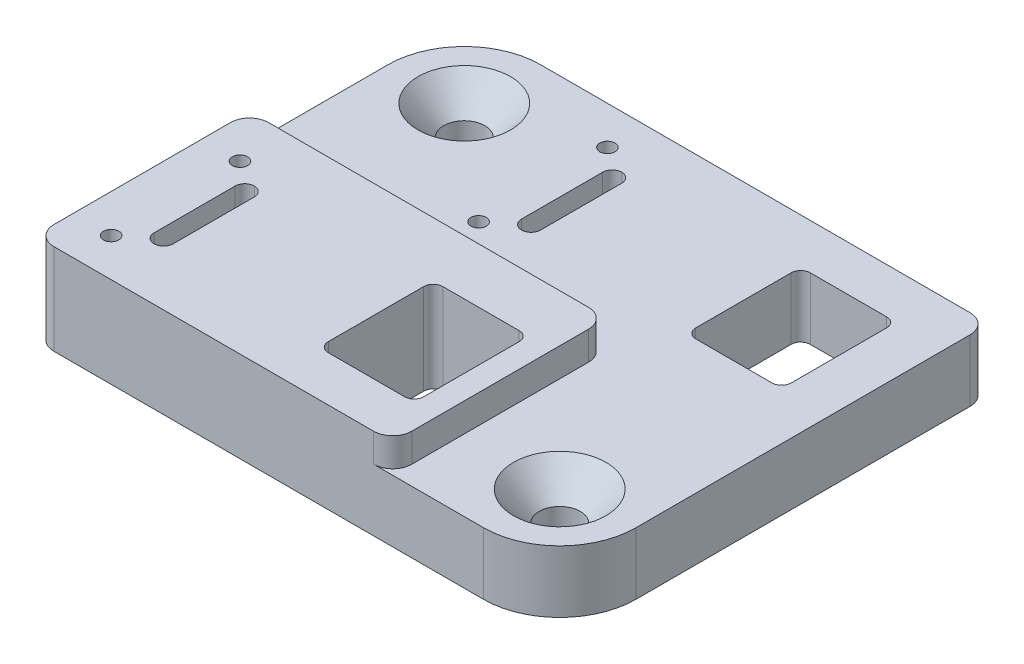
SolidWorks part; units mm, degrees
ref_plane "Top" through (0, 0, 0) normal (0, 0, 1) x (1, 0, 0)
ref_plane "Front" through (0, 0, 0) normal (0, 1, 0) x (1, 0, 0)
ref_plane "Right" through (0, 0, 0) normal (1, 0, 0) x (0, 0, -1)
sketch "Base Sketch" plane through (0, 0, 0) normal (0, 1, 0) x (1, 0, 0)
  line L1 (-27.5, 45) -> (27.5, 45)
  line L2 (-27.5, 45) -> (-27.5, 0)
  line L3 (-27.5, 0) -> (27.5, 0)
  line L4 (27.5, 45) -> (27.5, 0)
  dimension "D1" = 55
  dimension "D2" = 45
extrude "Base Extrude" add sketch "Base Sketch" against normal blind 6.5
sketch "Raised Section Sketch" plane through (0, 0, 0) normal (0, 1, 0) x (1, 0, 0)
  line L0 (-27.5, 45) -> (-27.5, 0) construction
  line L1 (-27.5, 0) -> (10, 0)
  line L2 (-27.5, 0) -> (-27.5, 22.5)
  line L3 (-27.5, 22.5) -> (10, 22.5)
  line L4 (10, 0) -> (10, 22.5)
  dimension "D1" = 37.5
extrude "Raised Section Extrude" add sketch "Raised Section Sketch" along normal blind 3
hole_wizard "Mosfet Mounting Holes" positions "Mosfet Mounting Holes Position Sketch" profile "Mosfet Mounting Holes Profile Sketch" hole size "M2x0.4" standard "ANSI Metric" end condition through all
sketch "Mosfet Mounting Holes Position Sketch" plane through (0, 3, 0) normal (0, 1, 0) x (1, 0, 0)
  line L0 (-23.5, 17.5) -> (-23.5, 4) construction
  line L2 (-8.5, 41) -> (-8.5, 27.5) construction
  line L4 (-27.5, 45) -> (-27.5, 22.5) construction
  line L5 (10, 0) -> (27.5, 0) construction
  line L6 (27.5, 45) -> (-27.5, 45) construction
  line L7 (27.5, 0) -> (27.5, 45) construction
  point P0 (-23.5, 4)
  point P2 (-23.5, 17.5)
  point P4 (-8.5, 27.5)
  point P6 (-8.5, 41)
  dimension "D1" = 13.5
  dimension "D2" = 36
sketch "Mosfet Mounting Holes Profile Sketch" plane through (-23.5, 3, -4) normal (1, 0, 0) x (0, 0, 1)
  line L0 (0, 0) -> (0, 9.5)
  line L1 (0, 9.5) -> (0.8, 9.5)
  line L2 (0.8, 9.5) -> (0.8, 0)
  line L5 (0.8, 0) -> (0, 0)
  line L11 (0, -6.35) -> (0, 107.95) construction
  dimension "Thru Hole Dia." = 1.6
  dimension "Thru Hole Depth" = 9.5
hole_wizard "Mounting Holes" positions "Mounting Holes Position Sketch" profile "Mounting Hole Profile Sketch" countersink size "#6" standard "ANSI Inch" end condition through all
sketch "Mounting Holes Position Sketch" plane through (0, 0, 0) normal (0, 1, 0) x (1, 0, 0)
  line L0 (-27.5, 37.5) -> (27.5, 37.5) construction
  line L3 (-27.5, 7.5) -> (27.5, 7.5) construction
  line L7 (-27.5, 45) -> (-27.5, 22.5) construction
  line L8 (27.5, 0) -> (27.5, 45) construction
  line L9 (10, 0) -> (27.5, 0) construction
  line L10 (27.5, 45) -> (-27.5, 45) construction
  point P0 (-20, 37.5)
  point P2 (20, 7.5)
sketch "Mounting Hole Profile Sketch" plane through (-20, 0, -37.5) normal (1, 0, 0) x (0, 0, 1)
  line L0 (0, 0) -> (0, 6.5)
  line L1 (0, 6.5) -> (2.1526, 6.5)
  line L2 (2.1526, 6.5) -> (2.1526, 3.0998)
  line L3 (2.1526, 3.0998) -> (4.8472, 0)
  line L5 (4.8472, 0) -> (0, 0)
  line L6 (-2.1526, 3.0998) -> (-4.8472, 0) construction
  line L11 (0, -6.35) -> (0, 107.95) construction
  dimension "Thru Hole Dia." = 4.3053
  dimension "Thru Hole Depth" = 6.5
  dimension "Near C'Sink Dia." = 9.6945
  dimension "Near C'Sink Angle" = 82
sketch "Pin Sketch" plane through (0, 0, 0) normal (0, 1, 0) x (1, 0, 0)
  line L0 (-23.5, 17.5) -> (-23.5, 4) construction
  line L1 (-2.5, 16.75) -> (7.5, 16.75)
  line L2 (-2.5, 16.75) -> (-2.5, 4.75)
  line L3 (-2.5, 4.75) -> (7.5, 4.75)
  line L4 (7.5, 16.75) -> (7.5, 4.75)
  line L5 (-23.5, 10.75) -> (-2.5, 10.75) construction
  line L6 (-8.5, 34.25) -> (12.5, 34.25) construction
  line L7 (-8.5, 41) -> (-8.5, 27.5) construction
  line L8 (12.5, 40.25) -> (22.5, 40.25)
  line L9 (12.5, 40.25) -> (12.5, 28.25)
  line L10 (12.5, 28.25) -> (22.5, 28.25)
  line L11 (22.5, 40.25) -> (22.5, 28.25)
  line L13 (-19.5, 16) -> (-21.5, 16)
  line L14 (-19.5, 16) -> (-19.5, 5.5)
  line L15 (-19.5, 5.5) -> (-21.5, 5.5)
  line L16 (-21.5, 16) -> (-21.5, 5.5)
  line L17 (-19.5, 16) -> (-21.5, 5.5) construction
  line L18 (-19.5, 5.5) -> (-21.5, 16) construction
  line L19 (-4.5, 39.5) -> (-6.5, 39.5)
  line L20 (-4.5, 39.5) -> (-4.5, 29)
  line L21 (-4.5, 29) -> (-6.5, 29)
  line L22 (-6.5, 39.5) -> (-6.5, 29)
  line L23 (-4.5, 39.5) -> (-6.5, 29) construction
  line L24 (-4.5, 29) -> (-6.5, 39.5) construction
  point P14 (-20.5, 10.75)
  point P21 (-5.5, 29)
  point P22 (2.5, 16.75)
  point P24 (-20.5, 5.5)
  point P26 (-5.5, 34.25)
  dimension "D1" = 10
  dimension "D2" = 26
  dimension "D3" = 12
  dimension "D4" = 2
  dimension "D5" = 3
  dimension "D6" = 10.5
  dimension "D7" = 3
extrude "Cut Pin Relief" cut sketch "Pin Sketch" against normal through all and the other way through all
fillet "Large Outside Corner Fillets" radius 8 2 edges at (-27.5, -3.25, -45) (27.5, -3.25, 0)
fillet "Small Outside Corner Fillets" radius 2 5 edges at (-27.5, -1.75, 0) (27.5, -3.25, -45) (10, 1.5, 0) (10, 1.5, -22.5) (-27.5, 1.5, -22.5)
fillet "Screw Terminal Cutout Fillets" radius 1 8 edges at (7.5, -1.75, -16.75) (-2.5, -1.75, -16.75) (-2.5, -1.75, -4.75) (7.5, -1.75, -4.75) (22.5, -3.25, -28.25) (12.5, -3.25, -28.25) (12.5, -3.25, -40.25) (22.5, -3.25, -40.25)
fillet "Header Pins Cutout Relief Fillets" radius 1 8 edges at (-4.5, -3.25, -29) (-6.5, -3.25, -29) (-6.5, -3.25, -39.5) (-4.5, -3.25, -39.5) (-19.5, -1.75, -16) (-21.5, -1.75, -16) (-21.5, -1.75, -5.5) (-19.5, -1.75, -5.5)
